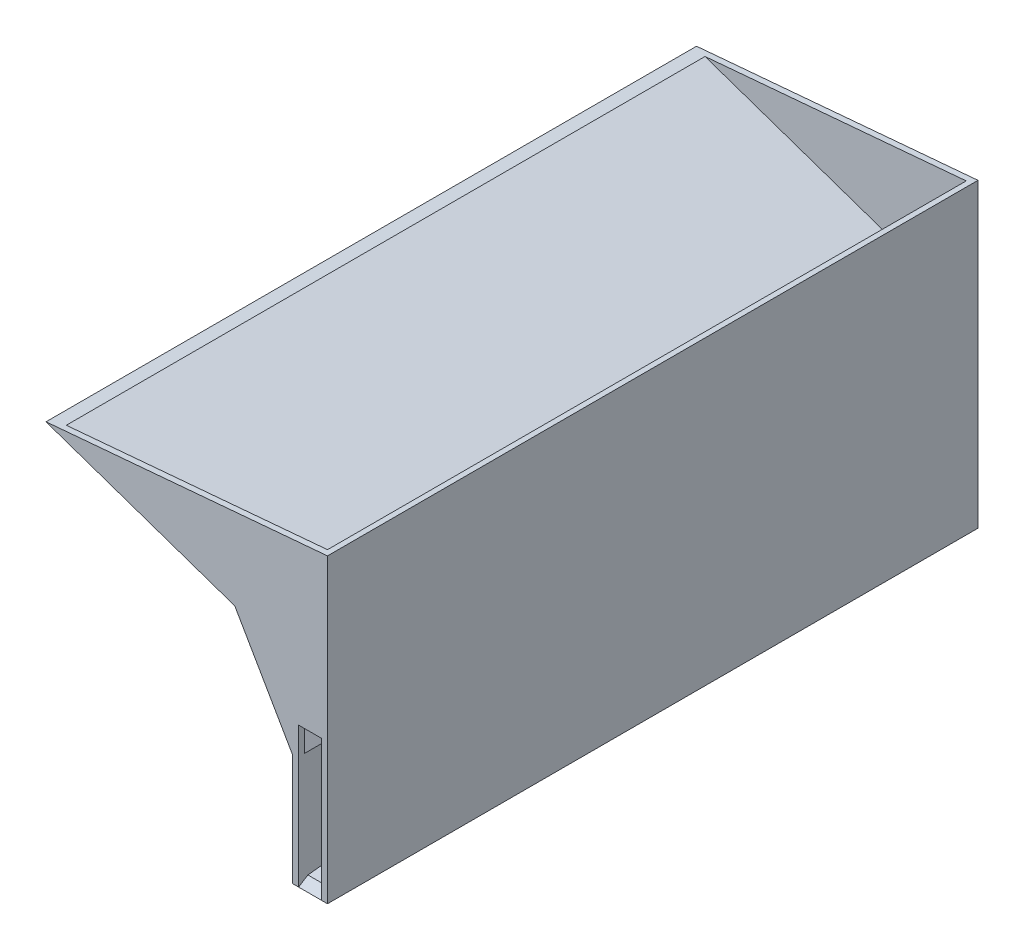
SolidWorks part; units mm, degrees
ref_plane "Front Plane" through (0, 0, 0) normal (0, 0, 1) x (1, 0, 0)
ref_plane "Top Plane" through (0, 0, 0) normal (0, 1, 0) x (1, 0, 0)
ref_plane "Right Plane" through (0, 0, 0) normal (1, 0, 0) x (0, 0, -1)
sketch "Sketch2" plane through (0, 0, 0) normal (0, 0, 1) x (1, 0, 0)
  line L0 (0, 0) -> (-125, 216.5064)
  line L1 (-125, 216.5064) -> (-532.2803, 356.8699)
  line L2 (-532.2803, 356.8699) -> (75, 410)
  line L3 (75, 410) -> (75, -240)
  line L4 (75, -240) -> (0, -240)
  line L5 (0, -240) -> (0, 0)
  point P6 (-86.9378, 57.4257)
  point P8 (-90.1349, 43.1615)
  point P9 (-84.4784, 55.3352)
  point P10 (-79.3138, 65.5415)
  point P11 (-69.9683, 43.8993)
  dimension "D1" = 150
  dimension "D2" = 609.6
  dimension "D3" = 650
  dimension "D4" = 240
  dimension "D5" = 75
  dimension "D6" = 250
  dimension "D7" = 275
extrude "Boss-Extrude1" add sketch "Sketch2" along normal mid plane 1403.35
shell "Shell1" thickness 12.7
sketch "Sketch3" plane through (0, 0, 701.675) normal (0, 0, 1) x (1, 0, 0)
  line L1 (12.7, -227.3) -> (62.3, -227.3)
  line L2 (12.7, -227.3) -> (12.7, 62.7)
  line L3 (12.7, 62.7) -> (62.3, 62.7)
  line L4 (62.3, -227.3) -> (62.3, 62.7)
  line L6 (0, -240) -> (75, -240) construction
  point P6 (37.5, -240)
  point P7 (37.5, -227.3)
  dimension "D1" = 49.6
  dimension "D2" = 12.7
  dimension "D3" = 290
extrude "Cut-Extrude1" cut sketch "Sketch3" against normal blind 20
sketch "Sketch4" plane through (12.7, 0, 0) normal (1, 0, 0) x (0, 0, -1)
  line L0 (688.975, -227.3) -> (688.975, -83.2389)
  line L1 (688.975, -83.2389) -> (-681.675, -227.3)
  line L2 (-681.675, -227.3) -> (688.975, -227.3)
  line L3 (701.675, -240) -> (701.675, 410) construction
  line L4 (-701.675, -240) -> (701.675, -240) construction
  line L5 (-701.675, -240) -> (-701.675, 410) construction
  dimension "D1" = 12.7
  dimension "D2" = 12.7
  dimension "D3" = 20
  dimension "D4" = 6
extrude "Boss-Extrude2" add sketch "Sketch4" along normal up to surface (49.6 mm away)
chamfer "Chamfer1" distance 12.7 distance2 20 3 edges at (12.7, -227.3, 691.675) (62.3, -227.3, 691.675) (37.5, -227.3, 701.675)
